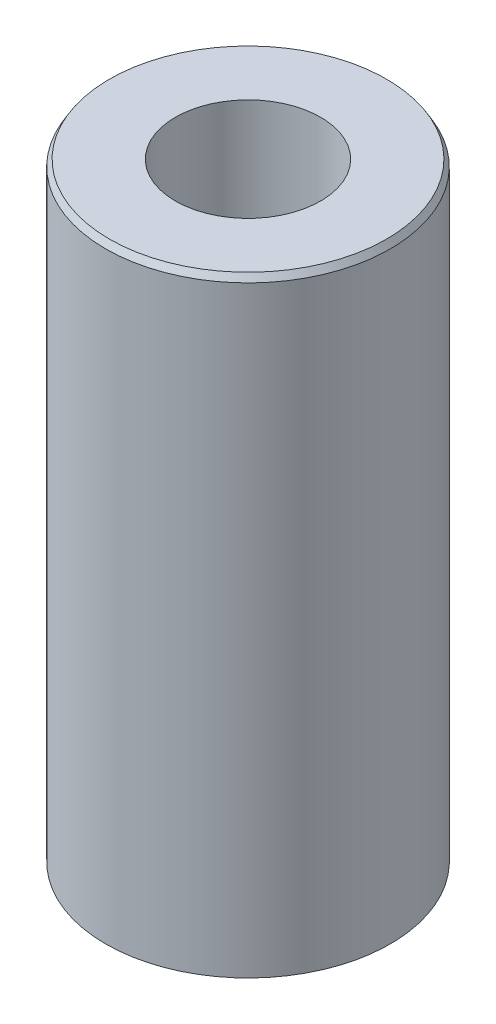
SolidWorks part; units mm, degrees
ref_plane "Front Plane" through (0, 0, 0) normal (0, 0, 1) x (1, 0, 0)
ref_plane "Top Plane" through (0, 0, 0) normal (0, 1, 0) x (1, 0, 0)
ref_plane "Right Plane" through (0, 0, 0) normal (1, 0, 0) x (0, 0, -1)
sketch "Sketch1" plane through (0, 0, 0) normal (0, 1, 0) x (1, 0, 0)
  circle A0 centre (0, 0) radius 52.5
  dimension "SHAFT_OD" = 105
extrude "Boss-Extrude1" add sketch "Sketch1" along normal blind 225.8327
sketch "Sketch2" plane through (0, 0, 0) normal (0, 1, 0) x (1, 0, 0)
  circle A0 centre (0, 0) radius 26.7833
  dimension "BORE_D" = 53.5665
extrude "Cut-Extrude1" cut sketch "Sketch2" along normal through all
chamfer "Chamfer1" distance 2.419 angle 30 2 edges at (0, 225.8327, 52.5) (0, 0, 52.5) first distance on face at (0, 225.8327, 52.5) first distance on face at (0, 0, 26.7833)
